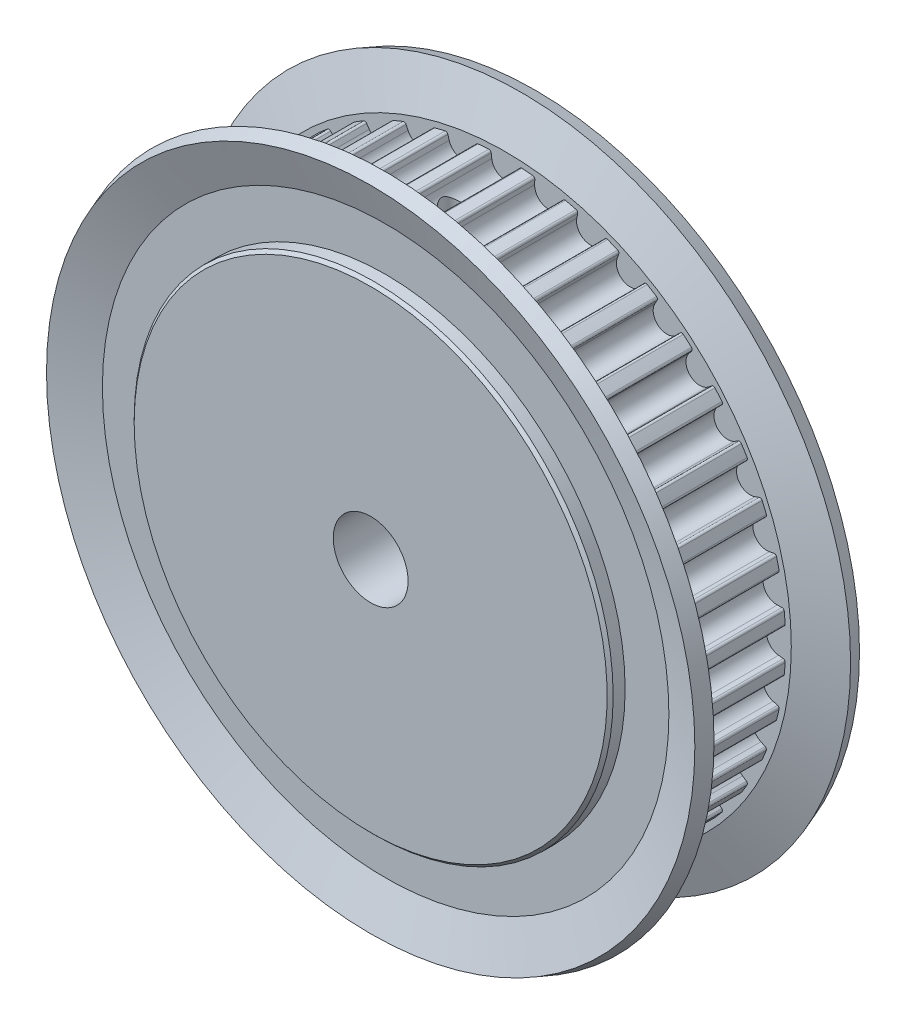
SolidWorks part; units mm, degrees
ref_plane "前视基准面" through (0, 0, 0) normal (0, 0, 1) x (1, 0, 0)
ref_plane "上视基准面" through (0, 0, 0) normal (0, 1, 0) x (1, 0, 0)
ref_plane "右视基准面" through (0, 0, 0) normal (1, 0, 0) x (0, 0, -1)
sketch "草图1" plane through (0, 0, 0) normal (1, 0, 0) x (0, 0, -1)
  line L0 (-34.7811, 0) -> (33.6192, 0) construction
  line L1 (0, 52.9736) -> (0, -62.0281) construction
  line L2 (-3.5, 18.72) -> (-3.5, 19.1)
  line L3 (-3.5, 19.1) -> (-4.5609, 22)
  line L4 (-4.5609, 22) -> (-5.5, 21.6564)
  line L5 (-5.5, 21.6564) -> (-4.5, 18.9228)
  line L6 (-4.5, 18.9228) -> (-4.5, 16)
  line L7 (-4.5, 16) -> (-5.5, 16)
  line L8 (4.5, 16) -> (5.5, 16)
  line L9 (4.5, 18.9228) -> (4.5, 16)
  line L10 (5.5, 21.6564) -> (4.5, 18.9228)
  line L11 (4.5609, 22) -> (5.5, 21.6564)
  line L12 (3.5, 19.1) -> (4.5609, 22)
  line L13 (3.5, 18.72) -> (3.5, 19.1)
  line L14 (3.5, -18.72) -> (3.5, -19.1)
  line L15 (3.5, -19.1) -> (4.5609, -22)
  line L16 (4.5609, -22) -> (5.5, -21.6564)
  line L17 (5.5, -21.6564) -> (4.5, -18.9228)
  line L18 (4.5, -18.9228) -> (4.5, -16)
  line L19 (4.5, -16) -> (5.5, -16)
  line L20 (-4.5, -16) -> (-5.5, -16)
  line L21 (-4.5, -18.9228) -> (-4.5, -16)
  line L22 (-5.5, -21.6564) -> (-4.5, -18.9228)
  line L23 (-4.5609, -22) -> (-5.5, -21.6564)
  line L24 (-3.5, -19.1) -> (-4.5609, -22)
  line L25 (-3.5, -18.72) -> (-3.5, -19.1)
  line L26 (-5.5, 16) -> (-5.5, -16)
  line L27 (5.5, 16) -> (5.5, -16)
  line L28 (-3.5, 18.72) -> (3.5, 18.72)
  line L29 (-3.5, -18.72) -> (3.5, -18.72)
  point P33 (0, 18.72)
  dimension "D1" = 2
  dimension "F" = 44
  dimension "D2" = 1
  dimension "E" = 32
  dimension "D3" = 1
  dimension "W" = 11
  dimension "D4" = 38.2
  dimension "A" = 7
  dimension "D5" = 37.44
sketch "草图2" plane through (0, 0, 0) normal (0, 0, 1) x (1, 0, 0)
  line L0 (-18.7064, 0) -> (19.5832, 0) construction
  line L1 (0, 30.5033) -> (0, -25.8377) construction
  line L2 (0, 0) -> (0, 18.72) construction
  line L3 (0.9121, 18.2469) -> (0.95, 18.5557)
  line L7 (0, 52.9736) -> (0, -62.0281) construction
  line L8 (-1.5, 2) -> (-1.5, 3.9)
  line L9 (1.5, 2) -> (1.5, 3.9)
  line L10 (-1.5, 3.9) -> (1.5, 3.9)
  line L11 (-0.9121, 18.2469) -> (-0.95, 18.5557)
  circle A0 centre (0, 0) radius 18.72
  circle A1 centre (0, 0) radius 19.1 construction
  circle A6 centre (0, 0) radius 2.5
  circle A7 centre (0, 0) radius 2.5
  arc A11 (-0.9121, 18.2469) -> (0.9121, 18.2469) centre (0, 18.3589) ccw
  arc A12 (-0.95, 18.5557) -> (-1.1078, 18.6872) centre (-1.0989, 18.5375) ccw
  arc A13 (0.95, 18.5557) -> (1.1078, 18.6872) centre (1.0989, 18.5375) cw
  point P7 (0, 19.1)
  point P8 (0, 18.72)
  point P13 (18.72, 0)
  dimension "PD" = 38.2
  dimension "OD" = 37.44
  dimension "H" = 5
  dimension "N" = 5
  dimension "D3" = 0.3
  dimension "D4" = 1.28
  dimension "D5" = 1.9
  dimension "D1" = 7
  dimension "b" = 3
  dimension "t" = 1.4
sketch "草图3" plane through (0, 0, 0) normal (1, 0, 0) x (0, 0, -1)
  line L0 (-5.5, 16) -> (-5.5, -16) construction
  line L1 (5.5, 16) -> (5.5, -16) construction
  line L2 (5.5, 21.6564) -> (4.5, 18.9228) construction
  line L3 (4.5, 16) -> (5.5, 16) construction
  line L4 (4.5, 18.9228) -> (4.5, 16) construction
  line L5 (-4.5, 18.9228) -> (-4.5, 16) construction
  line L6 (-5.5, 16) -> (-5.5, 0)
  line L7 (5.5, 16) -> (5.5, 0)
  line L8 (4.5609, 22) -> (5.5, 21.6564) construction
  line L9 (4.5, 16) -> (5.5, 16)
  line L10 (4.5, 18.9228) -> (4.5, 16)
  line L11 (-4.5, 18.9228) -> (-4.5, 16)
  line L12 (3.5, 19.1) -> (4.5609, 22) construction
  line L13 (3.5, 18.72) -> (3.5, 19.1) construction
  line L14 (-3.5, 18.72) -> (3.5, 18.72) construction
  line L15 (-3.5, 18.72) -> (-3.5, 19.1) construction
  line L16 (-3.5, 19.1) -> (-4.5609, 22) construction
  line L17 (-4.5609, 22) -> (-5.5, 21.6564) construction
  line L18 (-5.5, 21.6564) -> (-4.5, 18.9228) construction
  line L19 (5.5, 21.6564) -> (4.5, 18.9228)
  line L20 (4.5609, 22) -> (5.5, 21.6564)
  line L21 (3.5, 19.1) -> (4.5609, 22)
  line L22 (3.5, 18.72) -> (3.5, 19.1)
  line L23 (-3.5, 18.72) -> (3.5, 18.72)
  line L24 (-3.5, 18.72) -> (-3.5, 19.1)
  line L25 (-3.5, 19.1) -> (-4.5609, 22)
  line L26 (-4.5609, 22) -> (-5.5, 21.6564)
  line L27 (-5.5, 21.6564) -> (-4.5, 18.9228)
  line L28 (-34.7811, 0) -> (33.6192, 0) construction
  line L29 (-34.7811, 0) -> (33.6192, 0) construction
  line L30 (-5.5, 0) -> (5.5, 0)
  line L31 (-4.5, 16) -> (-5.5, 16) construction
  line L32 (-4.5, 16) -> (-5.5, 16)
revolve "旋转1" add sketch "草图3" angle 360 about L29
sketch "草图4" plane through (0, 0, 0) normal (0, 0, 1) x (1, 0, 0)
  line L3 (-0.9121, 18.2469) -> (-0.95, 18.5557) construction
  line L4 (0.9121, 18.2469) -> (0.95, 18.5557) construction
  line L5 (-0.9121, 18.2469) -> (-0.95, 18.5557)
  line L6 (0.9121, 18.2469) -> (0.95, 18.5557)
  arc A5 (-0.95, 18.5557) -> (-1.1078, 18.6872) centre (-1.0989, 18.5375) ccw construction
  arc A6 (-0.9121, 18.2469) -> (0.9121, 18.2469) centre (0, 18.3589) ccw construction
  circle A7 centre (0, 0) radius 18.72 construction
  arc A8 (1.1078, 18.6872) -> (0.95, 18.5557) centre (1.0989, 18.5375) ccw construction
  arc A9 (-0.95, 18.5557) -> (-1.1078, 18.6872) centre (-1.0989, 18.5375) ccw
  arc A10 (-0.9121, 18.2469) -> (0.9121, 18.2469) centre (0, 18.3589) ccw
  arc A11 (1.1078, 18.6872) -> (-1.1078, 18.6872) centre (0, 0) ccw
  arc A12 (1.1078, 18.6872) -> (0.95, 18.5557) centre (1.0989, 18.5375) ccw
extrude "切除-拉伸1" cut sketch "草图4" along normal up to vertex (3.5 mm away) from vertex up to point (0, 18.72, 3.5) starting at point (0, 18.72, -3.5)
pattern_circular "阵列(圆周)1" count 40 over 360 about axis through (0, 0, 34.7811) along (0, 0, 1) of "切除-拉伸1"
sketch "草图5" plane through (0, 0, 0) normal (0, 0, 1) x (1, 0, 0)
  circle A0 centre (0, 0) radius 2.5 construction
  circle A1 centre (0, 0) radius 2.5
extrude "H" [suppressed] cut sketch "草图5" along normal up to vertex from vertex up to point (0, 16, 5.5) starting at point (0, 16, -5.5)
sketch "草图6" plane through (0, 0, 0) normal (0, 0, 1) x (1, 0, 0)
  line L0 (-1.5, 3.9) -> (1.5, 3.9) construction
  line L1 (1.5, 2) -> (1.5, 3.9) construction
  line L2 (-1.5, 2) -> (-1.5, 3.9) construction
  line L3 (-1.5, 3.9) -> (1.5, 3.9)
  line L4 (1.5, 2) -> (1.5, 3.9)
  line L5 (-1.5, 2) -> (-1.5, 3.9)
  circle A0 centre (0, 0) radius 2.5 construction
  arc A1 (-1.5, 2) -> (1.5, 2) centre (0, 0) ccw
extrude "N" cut sketch "草图6" along normal up to vertex (5.5 mm away) from vertex up to point (0, 16, 5.5) starting at point (0, 16, -5.5)
sketch "草图8" plane through (0, 0, 0) normal (0, 0, 1) x (1, 0, 0)
  line L0 (-1.5, 2) -> (-1.5, 3.9) construction
  line L1 (-1.5, 3.9) -> (1.5, 3.9) construction
  line L2 (1.5, 2) -> (1.5, 3.9) construction
  line L3 (-1.5, 2) -> (-1.5, 3.9)
  line L4 (-1.5, 3.9) -> (1.5, 3.9)
  line L5 (1.5, 2) -> (1.5, 3.9)
  circle A0 centre (0, 0) radius 2.5 construction
  arc A1 (1.5, 2) -> (-1.5, 2) centre (0, 0) ccw
extrude "P" add sketch "草图8" along normal up to vertex from vertex up to point (0, 16, 5.5) starting at point (0, 16, -5.5)
sketch "草图7" plane through (0, 0, 0) normal (0, 1, 0) x (1, 0, 0)
  circle A0 centre (0, 0) radius 0.75
  dimension "M" = 1.5
extrude "螺纹孔1" cut sketch "草图7" along normal up to vertex up to point (0, 18.72, 0)
cosmetic thread "装饰螺纹线1" parameters "D2"=1.6
pattern_circular "螺纹孔2" count 2 every 120 about axis through (0, 0, 34.7811) along (0, 0, 1) of "螺纹孔1" reverse direction yes
chamfer "倒角1" distance 0.2 angle 45 2 edges at (16, 0, -5.5) (16, 0, 5.5)
